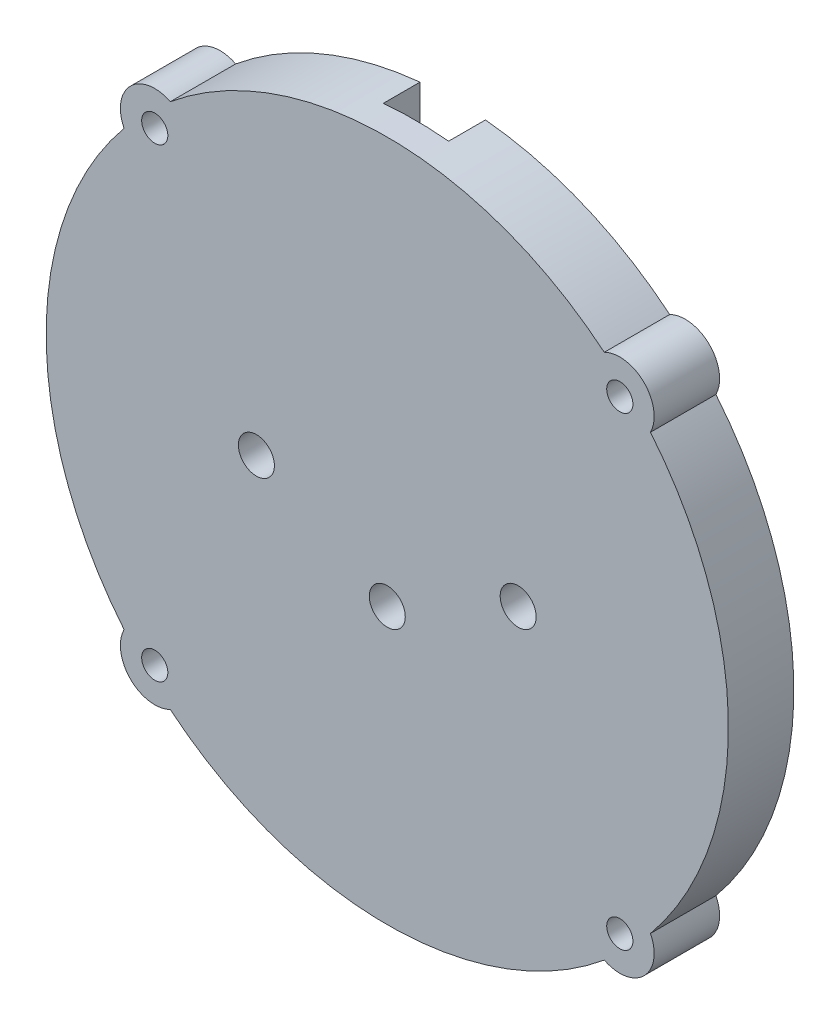
SolidWorks part; units mm, degrees
ref_plane "Front Plane" through (0, 0, 0) normal (0, 0, 1) x (1, 0, 0)
ref_plane "Top Plane" through (0, 0, 0) normal (0, 1, 0) x (1, 0, 0)
ref_plane "Right Plane" through (0, 0, 0) normal (1, 0, 0) x (0, 0, -1)
sketch "Sketch1" plane through (0, 0, 0) normal (0, 0, 1) x (1, 0, 0)
  line L0 (0, 62.8997) -> (0, -49.5687) construction
  line L5 (-81.1125, 0) -> (72.4755, 0) construction
  line L8 (0, 0) -> (-15.8735, 15.8735) construction
  line L13 (-4.2828, 9.374) -> (-9.4752, 14.5664)
  line L14 (-14.5664, 9.4752) -> (-9.374, 4.2828)
  line L15 (14.5664, 9.4752) -> (9.374, 4.2828)
  line L16 (4.2828, 9.374) -> (9.4752, 14.5664)
  line L17 (14.5664, -9.4752) -> (9.374, -4.2828)
  line L18 (4.2828, -9.374) -> (9.4752, -14.5664)
  line L19 (-4.2828, -9.374) -> (-9.4752, -14.5664)
  line L20 (-14.5664, -9.4752) -> (-9.374, -4.2828)
  line L22 (-7.1, -3.85) -> (7.1, -3.85)
  line L23 (-7.1, -3.85) -> (-7.1, 3.85)
  line L24 (-7.1, 3.85) -> (7.1, 3.85) construction
  line L25 (7.1, -3.85) -> (7.1, 3.85)
  line L26 (-7.1, -3.85) -> (7.1, 3.85) construction
  line L27 (-7.1, 3.85) -> (7.1, -3.85) construction
  line L28 (-7.1, 3.85) -> (7.1, 3.85) construction
  line L29 (-7.1, 3.85) -> (-7.1, 7.6)
  line L30 (-7.1, 7.6) -> (7.1, 7.6)
  line L31 (7.1, 3.85) -> (7.1, 7.6)
  line L33 (-4, 41.5077) -> (-4, 7.6)
  line L34 (-4, 7.6) -> (4, 7.6)
  line L35 (4, 41.5077) -> (4, 7.6)
  circle A5 centre (0, 0) radius 17 construction
  arc A6 (-9.4752, 14.5664) -> (-14.5664, 9.4752) centre (-12.0208, 12.0208) ccw
  arc A7 (9.4752, 14.5664) -> (14.5664, 9.4752) centre (12.0208, 12.0208) cw
  arc A8 (-9.4752, -14.5664) -> (-14.5664, -9.4752) centre (-12.0208, -12.0208) cw
  arc A9 (9.4752, -14.5664) -> (14.5664, -9.4752) centre (12.0208, -12.0208) ccw
  arc A10 (-4.2828, 9.374) -> (4.2828, 9.374) centre (0, 13.6569) ccw
  arc A11 (-4.2828, -9.374) -> (4.2828, -9.374) centre (0, -13.6569) cw
  arc A12 (9.374, 4.2828) -> (9.374, -4.2828) centre (13.6569, 0) ccw
  arc A13 (-9.374, 4.2828) -> (-9.374, -4.2828) centre (-13.6569, 0) cw
  circle A18 centre (0, 0) radius 34.5 construction
  circle A19 centre (0, 0) radius 40.2 construction
  arc A20 (-32.173, 26.529) -> (-32.173, -26.529) centre (0, 0) ccw
  arc A21 (-26.529, 32.173) -> (-32.173, 26.529) centre (-28.4257, 28.4257) ccw
  circle A22 centre (-28.4257, 28.4257) radius 1.6
  arc A23 (32.173, 26.529) -> (26.529, 32.173) centre (28.4257, 28.4257) ccw
  circle A24 centre (28.4257, 28.4257) radius 1.6
  arc A25 (26.529, -32.173) -> (32.173, -26.529) centre (28.4257, -28.4257) ccw
  circle A26 centre (28.4257, -28.4257) radius 1.6
  arc A27 (-32.173, -26.529) -> (-26.529, -32.173) centre (-28.4257, -28.4257) ccw
  circle A28 centre (-28.4257, -28.4257) radius 1.6
  arc A29 (32.173, -26.529) -> (32.173, 26.529) centre (0, 0) ccw
  arc A30 (-26.529, -32.173) -> (26.529, -32.173) centre (0, 0) ccw
  arc A32 (26.529, 32.173) -> (-26.529, 32.173) centre (0, 0) ccw
  point P64 (0, 0)
  dimension "D5" = 34
  dimension "D6" = 45
  dimension "D8" = 15.2
  dimension "D9" = 4
  dimension "D10" = 14.2
  dimension "D13" = 69
  dimension "D2" = 1.5
  dimension "D3" = 8.4
  dimension "D4" = 1.5
  dimension "D14" = 3.2
  dimension "D15" = 41.2
  dimension "D7" = 7.2
  dimension "D11" = 7.7
  dimension "D12" = 8
extrude "Boss-Extrude1" add sketch "Sketch1" along normal blind 8 contours A32 A21 A20 A27 A30 A25 A29 A23
extrude "Cut-Extrude4" cut sketch "Sketch1<7>" along normal blind 1.7 contours L13 A6 L14 A13 L20 A8 L19 A11 L18 A9 L17 A12 L15 A7 L16 A10
sketch "Sketch1<7>" plane through (0, 0, 0) normal (0, 0, 1) x (1, 0, 0) same geometry as "Sketch1"
extrude "Cut-Extrude5" cut sketch "Sketch1<8>" along normal blind 7.4 contours L22 L25 L31 L30 L29 L23
sketch "Sketch1<8>" plane through (0, 0, 0) normal (0, 0, 1) x (1, 0, 0) same geometry as "Sketch1"
extrude "Cut-Extrude6" cut sketch "Sketch1<9>" along normal blind 4.5 contours L35 A32 L33 A10 | A10 L33 L30 | A10 L34 L35 region at (-3.0266, 8.041, 0) region at (0, 24.8526, 0) region at (3.0266, 8.041, 0)
sketch "Sketch1<9>" plane through (0, 0, 0) normal (0, 0, 1) x (1, 0, 0) same geometry as "Sketch1"
sketch "Sketch3" plane through (0, 0, 8) normal (0, 0, 1) x (1, 0, 0)
  line L0 (0, 14.5718) -> (0, -12.4658) construction
  line L5 (-20, 8) -> (20, 8) construction
  line L6 (-20, 8) -> (-20, -12) construction
  line L7 (-20, -12) -> (20, -12) construction
  line L8 (20, 8) -> (20, -12) construction
  line L9 (-23.2812, 0) -> (23.0311, 0) construction
  circle A0 centre (-16, 0) radius 2.2
  circle A1 centre (16, 0) radius 2.2
  circle A2 centre (0, -8) radius 2.2
  circle A3 centre (0, 0) radius 4 construction
  dimension "D4" = 4.4
  dimension "D7" = 8
  dimension "D1" = 40
  dimension "D2" = 8
  dimension "D3" = 12
  dimension "D5" = 4
  dimension "D6" = 4
extrude "Cut-Extrude7" cut sketch "Sketch3" against normal blind 6
extrude "Cut-Extrude8" cut sketch "Sketch1<10>" along normal through all contours A22 | A24 | A26 | A28
sketch "Sketch1<10>" plane through (0, 0, 0) normal (0, 0, 1) x (1, 0, 0) same geometry as "Sketch1"
